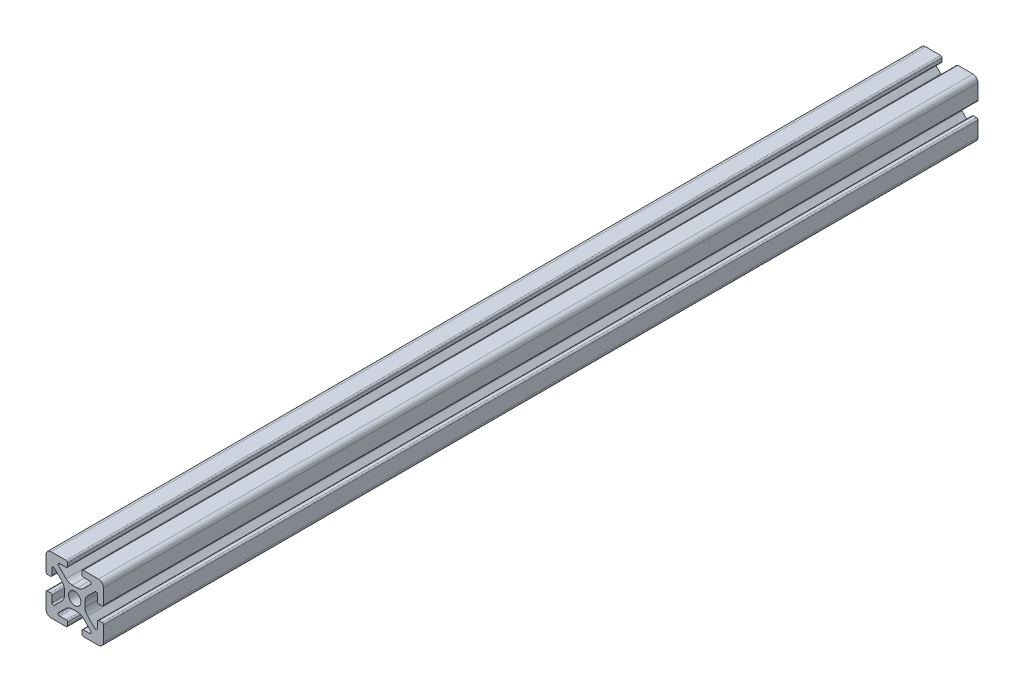
SolidWorks part; units mm, degrees
ref_plane "Front Plane" through (0, 0, 0) normal (0, 0, 1) x (1, 0, 0)
ref_plane "Top Plane" through (0, 0, 0) normal (0, 1, 0) x (1, 0, 0)
ref_plane "Right Plane" through (0, 0, 0) normal (1, 0, 0) x (0, 0, -1)
sketch "Sketch2" plane through (0, 0, 0) normal (0, 0, 1) x (1, 0, 0)
  line L0 (0, 10) -> (0, -10) construction
  line L1 (-10, 0) -> (10, 0) construction
  line L2 (2.5, -10) -> (10, -10)
  line L3 (10, -10) -> (10, -2.5)
  line L4 (2.5, -10) -> (2.5, -7.9246)
  line L5 (2.5, -7.9246) -> (6.4571, -7.9246)
  line L6 (6.4571, -7.9246) -> (2.1325, -3.6)
  line L7 (0, 0) -> (10, -10) construction
  line L8 (10, -2.5) -> (7.9246, -2.5)
  line L9 (7.9246, -2.5) -> (7.9246, -6.4571)
  line L10 (7.9246, -6.4571) -> (3.6, -2.1325)
  line L11 (5.7623, -4.2948) -> (4.2948, -5.7623) construction
  circle A0 centre (0, 0) radius 2.15
  arc A1 (5.25, -7.9246) -> (5.6036, -7.0711) centre (5.25, -7.4246) ccw construction
  point P8 (0, -3.6)
  point P16 (5.0286, -5.0286)
  dimension "Center Hole Diameter" = 4.3
  dimension "D3" = 0.5
  dimension "Rail Height" = 20
  dimension "Rail Width" = 20
  dimension "T-Slot Width" = 5
  dimension "Slot Depth" = 6.4
  dimension "Slot Inner Width" = 11.5
sketch "Sketch3" plane through (0, 0, 0) normal (1, 0, 0) x (0, 0, -1)
  line L0 (-152.4, -10) -> (152.4, -10) construction
  line L1 (-127, 0) -> (127, 0) construction
  line L2 (0, 10) -> (0, -10) construction
  line L3 (0, 10) -> (0, -10) construction
  point P6 (-127, 0)
  point P8 (127, 0)
  dimension "Length" = 304.8
  dimension "D1" = 25.4
sketch "Sketch4" plane through (0, 0, 0) normal (0, 0, 1) x (1, 0, 0)
  line L0 (3, -10) -> (8.25, -10)
  line L1 (2.5, -10) -> (10, -10) construction
  line L2 (2.5, -10) -> (2.5, -7.9246) construction
  line L3 (2.5, -7.9246) -> (6.4571, -7.9246) construction
  line L4 (2.5, -8.4246) -> (2.5, -9.5)
  line L5 (3, -7.9246) -> (5.25, -7.9246)
  line L6 (0, -3.6) -> (0.8898, -3.6)
  line L7 (6.4571, -7.9246) -> (2.1325, -3.6) construction
  line L8 (3.0112, -4.4787) -> (5.6036, -7.0711)
  line L9 (10, -10) -> (10, -2.5) construction
  line L10 (7.9246, -6.4571) -> (3.6, -2.1325) construction
  line L11 (7.9246, -2.5) -> (7.9246, -6.4571) construction
  line L12 (7.9246, -5.25) -> (7.9246, -3)
  line L13 (10, -2.5) -> (7.9246, -2.5) construction
  line L14 (8.4246, -2.5) -> (9.5, -2.5)
  line L15 (10, -3) -> (10, -8.25)
  line L16 (7.0711, -5.6036) -> (4.4787, -3.0112)
  line L17 (3.6, 0) -> (3.6, -0.8898)
  line L18 (-10, 0) -> (10, 0) construction
  line L19 (0, -3.6) -> (0, -2.15)
  line L20 (0, 10) -> (0, -10) construction
  line L21 (3.6, 0) -> (2.15, 0)
  arc A0 (2.5, -9.5) -> (3, -10) centre (3, -9.5) ccw
  arc A1 (5.25, -7.9246) -> (5.6036, -7.0711) centre (5.25, -7.4246) ccw construction
  arc A2 (2.5, -8.4246) -> (3, -7.9246) centre (3, -8.4246) cw
  arc A3 (5.25, -7.9246) -> (5.6036, -7.0711) centre (5.25, -7.4246) ccw
  arc A4 (0.8898, -3.6) -> (3.0112, -4.4787) centre (0.8898, -6.6) cw
  arc A5 (8.25, -10) -> (10, -8.25) centre (8.25, -8.25) ccw
  arc A6 (7.0711, -5.6036) -> (7.9246, -5.25) centre (7.4246, -5.25) ccw
  arc A7 (7.9246, -3) -> (8.4246, -2.5) centre (8.4246, -3) cw
  arc A8 (9.5, -2.5) -> (10, -3) centre (9.5, -3) cw
  arc A9 (4.4787, -3.0112) -> (3.6, -0.8898) centre (6.6, -0.8898) cw
  circle A10 centre (0, 0) radius 2.15 construction
  arc A11 (0, -2.15) -> (2.15, 0) centre (0, 0) ccw
  dimension "D1" = 1.75
  dimension "D2" = 3
extrude "Boss-Extrude1" add sketch "Sketch4" along normal mid plane 304.8
mirror "Mirror1" about plane through (0, 0, 0) normal (1, 0, 0) of bodies 134
mirror "Mirror2" about plane through (0, 0, 0) normal (0, 1, 0) of bodies 135
equation "\"D3@Sketch2\"=\"T-Slot Width@Sketch2\"*0.1"
equation "\"D1@Sketch4\"=\"D3@Sketch2\"*3.5"
equation "\"D2@Sketch4\"=\"D3@Sketch2\"*6"
equation "\"D1@Boss-Extrude1\"=\"Length@Sketch3\""
